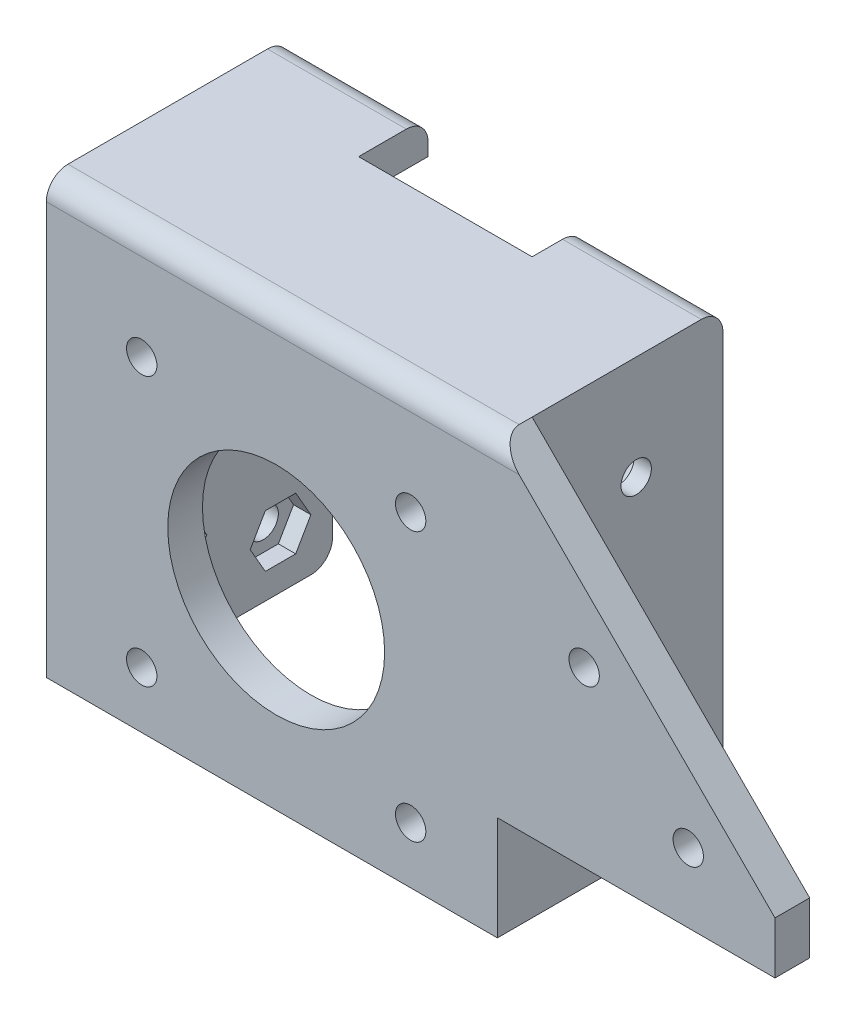
SolidWorks part; units mm, degrees
ref_plane "Front Plane" through (0, 0, 0) normal (0, 0, 1) x (1, 0, 0)
ref_plane "Top Plane" through (0, 0, 0) normal (0, 1, 0) x (1, 0, 0)
ref_plane "Right Plane" through (0, 0, 0) normal (1, 0, 0) x (0, 0, -1)
sketch "Sketch1" plane through (0, 0, 0) normal (0, 0, 1) x (1, 0, 0)
  line L0 (-50.3416, 0) -> (46.1674, 0) construction
  line L1 (0, -28.4394) -> (0, 79.8206) construction
  line L2 (57.5, 18) -> (25.5, 50)
  line L4 (-26.5, 0) -> (-26.5, 50)
  line L5 (-26.5, 50) -> (25.5, 50)
  line L6 (57.5, 12) -> (57.5, 18)
  line L7 (25.5, -2.2452) -> (25.5, 66.7313) construction
  line L10 (57.5, 12) -> (25.5, 12)
  line L11 (25.5, 12) -> (25.5, 0)
  line L12 (25.5, 0) -> (-26.5, 0)
  dimension "D1" = 50
  dimension "D2" = 38
  dimension "D3" = 6
  dimension "D5" = 25.5
  dimension "D6" = 45
  dimension "D7" = 52
extrude "Boss-Extrude1" add sketch "Sketch1" along normal blind 4
sketch "Sketch2" plane through (0, 0, 4) normal (0, 0, 1) x (1, 0, 0)
  line L0 (-39.1184, 22) -> (53.5, 22) construction
  line L1 (0, -8.7046) -> (0, 47.1631) construction
  line L2 (57.5, 18) -> (25.5, 50) construction
  line L3 (-15.5, 6.5) -> (15.5, 6.5) construction
  line L4 (-15.5, 6.5) -> (-15.5, 37.5) construction
  line L5 (-15.5, 37.5) -> (15.5, 37.5) construction
  line L6 (15.5, 6.5) -> (15.5, 37.5) construction
  line L7 (-15.5, 6.5) -> (15.5, 37.5) construction
  line L8 (-15.5, 37.5) -> (15.5, 6.5) construction
  line L9 (-26.5, 0) -> (25.5, 0) construction
  circle A0 centre (0, 22) radius 12.5
  circle A1 centre (15.5, 6.5) radius 1.75
  circle A2 centre (15.5, 37.5) radius 1.75
  circle A3 centre (-15.5, 37.5) radius 1.75
  circle A4 centre (-15.5, 6.5) radius 1.75
  point P4 (0, 22)
  dimension "D1" = 3.5
  dimension "D4" = 25
  dimension "D2" = 31
  dimension "D3" = 22
extrude "Cut-Extrude1" cut sketch "Sketch2" against normal through all
sketch "Sketch9" plane through (0, 0, 0) normal (0, 0, -1) x (-1, 0, 0)
  line L0 (-61, 20) -> (-35.5, 20) construction
  line L1 (-35.5, 20) -> (-35.5, 48.0747) construction
  line L2 (-25.5, -5.4794) -> (-25.5, 53.2688) construction
  line L3 (-25.5, 12) -> (-57.5, 12) construction
  circle A1 centre (-47.5, 20) radius 1.75
  circle A2 centre (-35.5, 32) radius 1.75
  dimension "D5" = 3.5
  dimension "D1" = 12
  dimension "D3" = 12
  dimension "D4" = 8
  dimension "D2" = 10
extrude "Cut-Extrude2" cut sketch "Sketch9" against normal blind 4
sketch "Sketch13" plane through (0, 0, 4) normal (0, 0, 1) x (1, 0, 0)
  line L8 (-26.5, 34.0255) -> (-46.5, 34.0255)
  line L9 (-26.5, 50) -> (-26.5, 0) construction
  line L10 (-46.5, 34.0255) -> (-46.5, 96.6007)
  line L11 (-46.5, 96.6007) -> (-32.0913, 96.6007)
  line L13 (57.5, 18) -> (25.5, 50) construction
  line L14 (25.5, 50) -> (19.5, 56)
  line L15 (-26.5, 34.0255) -> (-26.5, 50)
  line L17 (-32.0913, 96.6007) -> (-32.0913, 74.4017)
  line L20 (19.5, 56) -> (-3.8448, 56)
  line L21 (25.5, 50) -> (-26.5, 50)
  arc A3 (-3.8448, 56) -> (-32.0913, 74.4017) centre (-11.974, 74.4017) cw
  dimension "D1" = 20
  dimension "D2" = 6
extrude "Boss-Extrude7" [suppressed] add sketch "Sketch13" against normal blind 4
sketch "Sketch16" [suppressed] plane through (0, 0, 4) normal (0, 0, 1) x (1, 0, 0)
  line L0 (-38.5457, 92.6569) -> (2.0281, 52.0832) construction
  line L1 (-45, 34.0255) -> (-25, 34.0255) construction
  line L2 (-38.5457, 96.6007) -> (-38.5457, 85.5222) construction
  line L3 (-32.0913, 96.6007) -> (-45, 96.6007) construction
  circle A0 centre (2.0281, 52.0832) radius 2
  circle A1 centre (-38.5457, 92.6569) radius 2
  dimension "D3" = 4
  dimension "D1" = 57.38
  dimension "D2" = 45
extrude "Cut-Extrude6" [suppressed] cut sketch "Sketch16" against normal blind 4
sketch "Sketch17" plane through (0, 0, 0) normal (0, 0, -1) x (-1, 0, 0)
  line L0 (-25.5, 0) -> (-25.5, 50)
  line L2 (-25.5, 50) -> (26.5, 50)
  line L3 (26.5, 50) -> (26.5, 0) construction
  line L4 (26.5, 50) -> (26.5, 0)
  line L5 (26.5, 0) -> (21.5, 0)
  line L6 (26.5, 0) -> (-25.5, 0) construction
  line L7 (21.5, 0) -> (21.5, 46)
  line L8 (21.5, 46) -> (-21.5, 46)
  line L9 (-21.5, 46) -> (-21.5, 0)
  line L10 (-21.5, 0) -> (-25.5, 0)
  dimension "D1" = 43
  dimension "D2" = 21.5
  dimension "D3" = 4
extrude "Boss-Extrude8" add sketch "Sketch17" along normal blind 24
sketch "Sketch18" plane through (25.5, 0, 0) normal (1, 0, 0) x (0, 0, -1)
  line L0 (12, 4.8734) -> (12, 63.3892) construction
  circle A0 centre (12, 38) radius 1.75
  circle A1 centre (12, 20) radius 1.75
  dimension "D1" = 3.5
  dimension "D2" = 20
  dimension "D3" = 18
  dimension "D4" = 12
extrude "Cut-Extrude7" cut sketch "Sketch18" against normal up to surface (4 mm away) up to face at (21.5, 23, -12)
sketch "Sketch19" plane through (-26.5, 0, 0) normal (-1, 0, 0) x (0, 0, 1)
  line L0 (-6, 10) -> (-6, 45) construction
  line L2 (4, 0) -> (-24, 0) construction
  line L4 (-18, 6) -> (-6, 6) construction
  line L5 (-18, 6) -> (-18, 41) construction
  line L6 (-18, 41) -> (-6, 41) construction
  line L7 (-6, 6) -> (-6, 41) construction
  circle A0 centre (-18, 6) radius 1.75
  circle A2 centre (-18, 41) radius 1.75
  circle A5 centre (-6, 10) radius 1.75
  circle A6 centre (-6, 45) radius 1.75
  dimension "D5" = 3.5
  dimension "D4" = 12
  dimension "D2" = 6
  dimension "D3" = 35
  dimension "D1" = 6
  dimension "D6" = 35
  dimension "D7" = 10
extrude "Cut-Extrude8" cut sketch "Sketch19" against normal blind 10
sketch "Sketch20" plane through (0, 50, 0) normal (0, 1, 0) x (1, 0, 0)
  line L0 (-26.5, 24) -> (25.5, 24) construction
  line L1 (25.5, 24) -> (-10.5, 24)
  line L2 (25.5, 24) -> (25.5, 22)
  line L4 (-10.5, 24) -> (-10.5, 16)
  line L6 (25.5, 24) -> (25.5, 0) construction
  line L7 (-10.5, 16) -> (9.5, 16)
  line L8 (9.5, 16) -> (9.5, 22)
  line L9 (9.5, 22) -> (25.5, 22)
  dimension "D1" = 20
  dimension "D2" = 2
  dimension "D3" = 16
  dimension "D4" = 6
extrude "Cut-Extrude9" cut sketch "Sketch20" against normal up to surface (50 mm away) up to face at (-0.25, 0, -11)
fillet "Fillet1" radius 2.5 4 edges at (17.5, 50, -22) (-18.5, 50, -24) (23.5, 0, -22) (-24, 0, -24)
sketch "Sketch22" plane through (-21.5, 0, 0) normal (1, 0, 0) x (0, 0, -1)
  line L0 (21.5, 0) -> (0, 0) construction
  line L1 (7.75, 41.9689) -> (9.5, 45)
  line L2 (9.5, 45) -> (7.75, 48.0311)
  line L3 (7.75, 48.0311) -> (4.25, 48.0311)
  line L4 (4.25, 48.0311) -> (2.5, 45)
  line L5 (2.5, 45) -> (4.25, 41.9689)
  line L6 (4.25, 41.9689) -> (7.75, 41.9689)
  circle A0 centre (6, 45) radius 3.0311 construction
  point P0 (6, 45)
  dimension "D1" = 3.5
extrude "Cut-Extrude11" cut sketch "Sketch22" along normal blind 3 and the other way blind 2
sketch "Sketch23" plane through (-21.5, 0, 0) normal (1, 0, 0) x (0, 0, -1)
  line L0 (21.5, 0) -> (0, 0) construction
  line L1 (19.75, 37.9689) -> (21.5, 41)
  line L2 (21.5, 41) -> (19.75, 44.0311)
  line L3 (19.75, 44.0311) -> (16.25, 44.0311)
  line L4 (16.25, 44.0311) -> (14.5, 41)
  line L5 (14.5, 41) -> (16.25, 37.9689)
  line L6 (16.25, 37.9689) -> (19.75, 37.9689)
  line L7 (7.75, 6.9689) -> (9.5, 10)
  line L8 (9.5, 10) -> (7.75, 13.0311)
  line L9 (7.75, 13.0311) -> (4.25, 13.0311)
  line L10 (4.25, 13.0311) -> (2.5, 10)
  line L11 (2.5, 10) -> (4.25, 6.9689)
  line L12 (4.25, 6.9689) -> (7.75, 6.9689)
  line L13 (16.25, 2.9689) -> (19.75, 2.9689)
  line L14 (19.75, 2.9689) -> (21.5, 6)
  line L15 (21.5, 6) -> (19.75, 9.0311)
  line L16 (19.75, 9.0311) -> (16.25, 9.0311)
  line L17 (16.25, 9.0311) -> (14.5, 6)
  line L18 (14.5, 6) -> (16.25, 2.9689)
  circle A0 centre (18, 41) radius 3.0311 construction
  circle A1 centre (6, 10) radius 3.0311 construction
  circle A2 centre (18, 6) radius 3.0311 construction
  point P0 (18, 41)
  point P1 (18, 6)
  point P3 (6, 10)
  dimension "D1" = 3.5
extrude "Cut-Extrude12" cut sketch "Sketch23" against normal blind 2
sketch "Sketch24" plane through (21.5, 0, 0) normal (-1, 0, 0) x (0, 0, 1)
  line L0 (-19.5, 0) -> (0, 0) construction
  line L1 (-10.2403, 41.0479) -> (-13.7597, 41.0479)
  line L2 (-13.7597, 41.0479) -> (-15.5194, 38)
  line L3 (-15.5194, 38) -> (-13.7597, 34.9521)
  line L4 (-13.7597, 34.9521) -> (-10.2403, 34.9521)
  line L5 (-10.2403, 34.9521) -> (-8.4806, 38)
  line L6 (-8.4806, 38) -> (-10.2403, 41.0479)
  line L7 (-10.25, 23.0311) -> (-13.75, 23.0311)
  line L8 (-13.75, 23.0311) -> (-15.5, 20)
  line L9 (-15.5, 20) -> (-13.75, 16.9689)
  line L10 (-13.75, 16.9689) -> (-10.25, 16.9689)
  line L11 (-10.25, 16.9689) -> (-8.5, 20)
  line L12 (-8.5, 20) -> (-10.25, 23.0311)
  circle A0 centre (-12, 38) radius 3.0479 construction
  circle A1 centre (-12, 20) radius 3.0311 construction
  point P0 (-12, 38)
  point P1 (-12, 20)
  dimension "D1" = 3.5
extrude "Cut-Extrude13" cut sketch "Sketch24" against normal blind 2
fillet "Fillet2" radius 2.5 1 edges at (-0.5, 50, 4)
equation "\"motor_plate_thickness\"=4"
equation "\"D1@Boss-Extrude1\"=\"motor_plate_thickness\""
equation "\"motor_hub_diameter\"=25"
equation "\"D4@Sketch2\"=\"motor_hub_diameter\""
equation "\"motor_mount_hole_od\"=3.5"
equation "\"D1@Sketch2\"=\"motor_mount_hole_od\""
equation "\"motor_mount_hole_spacing\"=31"
equation "\"D2@Sketch2\"=\"motor_mount_hole_spacing\""
equation "\"D5@Sketch9\"=\"motor_mount_hole_od\""
equation "\"D1@Sketch18\"=\"motor_mount_hole_od\""
equation "\"D5@Sketch19\"=\"motor_mount_hole_od\""
